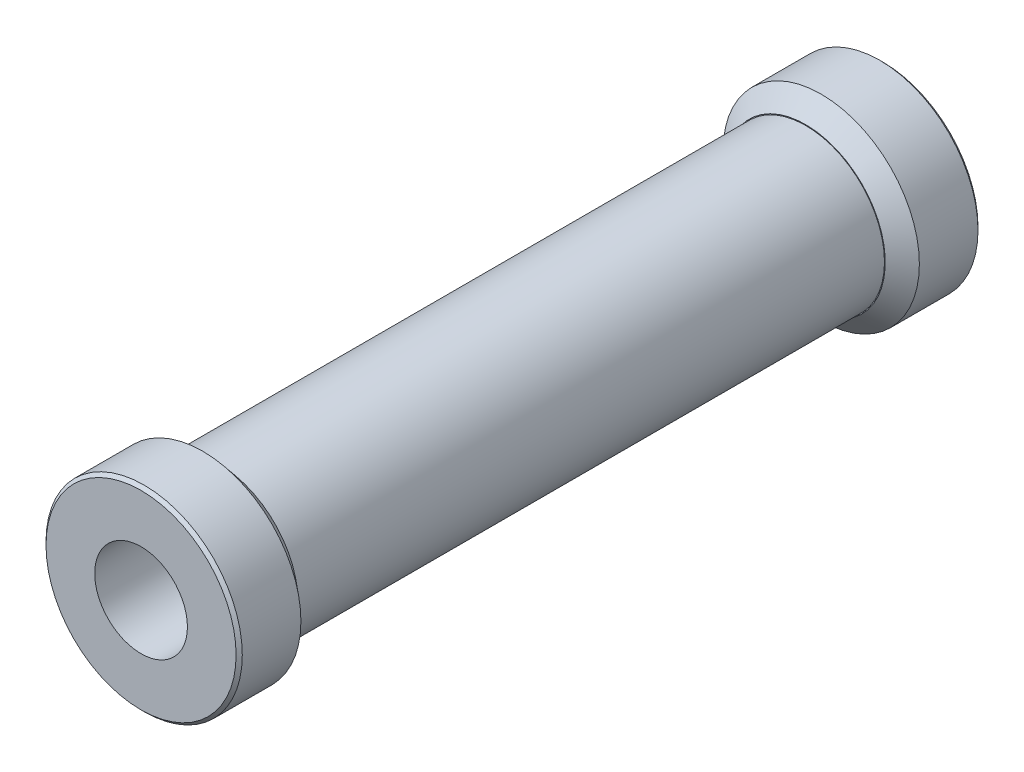
SolidWorks part; units mm, degrees
ref_plane "Ön Düzlem" through (0, 0, 0) normal (0, 0, 1) x (1, 0, 0)
ref_plane "Üst Düzlem" through (0, 0, 0) normal (0, 1, 0) x (1, 0, 0)
ref_plane "Sağ Düzlem" through (0, 0, 0) normal (1, 0, 0) x (0, 0, -1)
sketch "Çizim1" plane through (0, 0, 0) normal (1, 0, 0) x (0, 0, -1)
  line L0 (-15.5449, 0) -> (12.2551, 0) construction
  line L1 (-9.5, 0) -> (9.5, 0)
  line L2 (9.5, 0) -> (9.5, -2.55)
  line L7 (9.5, 0) -> (13.7667, 0)
  line L8 (9.5, -2.55) -> (-9.5, -2.55)
  line L9 (-9.5, -2.55) -> (-9.5, 0)
  point P5 (0, 0)
  dimension "D1" = 27.8
  dimension "D2" = 19
  dimension "D3" = 2.55
revolve "Döndür3" add sketch "Çizim1" angle 360 about L0 region at (0, -1.275, 0)
sketch "Çizim4" plane through (0, 0, -9.5) normal (0, 0, -1) x (-1, 0, 0)
  circle A0 centre (0, 0) radius 2.575
  dimension "D1" = 5.15
extrude "Yükseklik-Ekstrüzyon1" add sketch "Çizim4" along normal blind 0.6
sketch "Çizim5" plane through (0, 0, -10.1) normal (0, 0, -1) x (-1, 0, 0)
  circle A0 centre (0, 0) radius 3.175
  dimension "D1" = 6.35
extrude "Yükseklik-Ekstrüzyon2" add sketch "Çizim5" along normal blind 1.9
draft "Draft2" type of draft neutral plane draft angle 50 faces to draft 1 face at (-2.575, 0, -10.1) neutral plane through (0, 0, -9.5) neutral plane normal (0, 0, 1) parameters "D1"=50
sketch "Çizim7" plane through (0, 0, 9.5) normal (0, 0, 1) x (1, 0, 0)
  circle A0 centre (0, 0) radius 2.575
  dimension "D1" = 5.15
extrude "Yükseklik-Ekstrüzyon4" add sketch "Çizim7" along normal blind 0.6
sketch "Çizim8" plane through (0, 0, 10.1) normal (0, 0, 1) x (1, 0, 0)
  circle A0 centre (0, 0) radius 3.175
  dimension "D1" = 6.35
extrude "Yükseklik-Ekstrüzyon5" add sketch "Çizim8" along normal blind 1.9
draft "Draft3" type of draft neutral plane draft angle 50 faces to draft 1 face at (2.575, 0, 10.1) neutral plane through (0, 0, 9.5) neutral plane normal (0, 0, -1) parameters "D1"=50
sketch "Çizim9" plane through (0, 0, 12) normal (0, 0, 1) x (1, 0, 0)
  circle A0 centre (0, 0) radius 1.5
  dimension "D1" = 3
extrude "Kes-Ekstrüzyon1" cut sketch "Çizim9" against normal blind 100
chamfer "Pah1" distance 0.1 angle 45 2 edges at (3.175, 0, 12) (-3.175, 0, -12)
